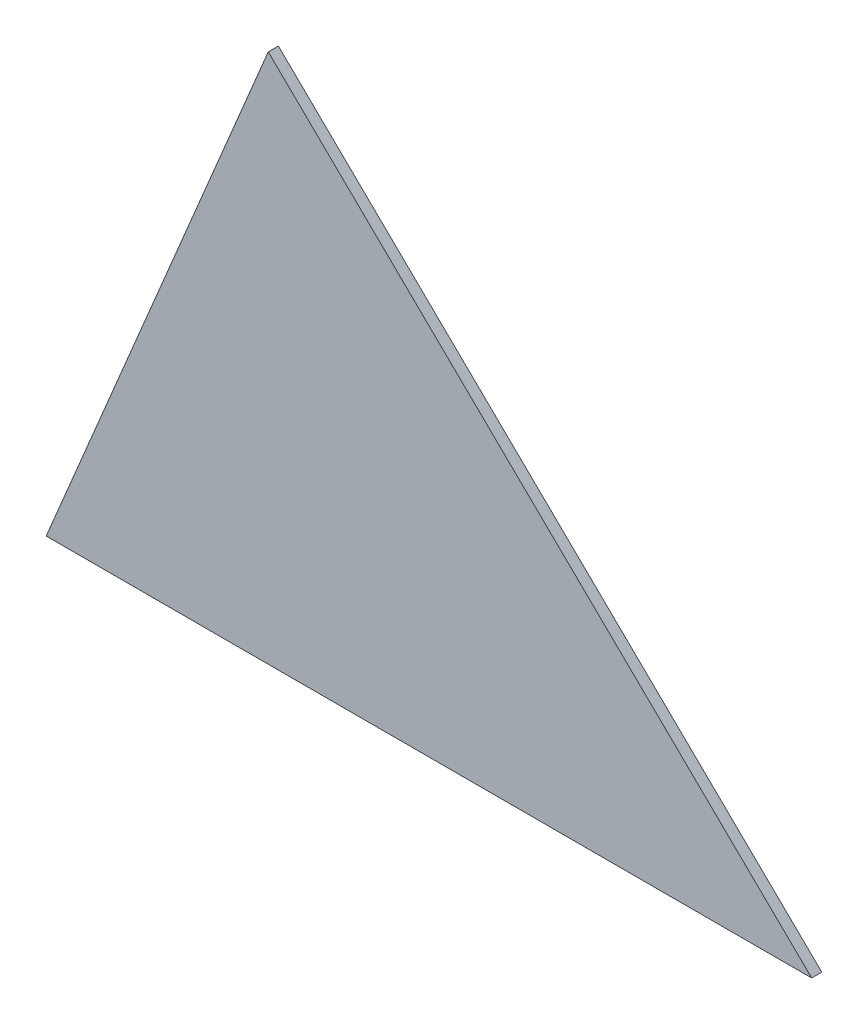
SolidWorks part; units mm, degrees
ref_plane "Front Plane" through (0, 0, 0) normal (0, 0, 1) x (1, 0, 0)
ref_plane "Top Plane" through (0, 0, 0) normal (0, 1, 0) x (1, 0, 0)
ref_plane "Right Plane" through (0, 0, 0) normal (1, 0, 0) x (0, 0, -1)
sketch "Sketch1" plane through (0, 0, 0) normal (0, 0, 1) x (1, 0, 0)
  line L0 (-7.9994, 30.3202) -> (-29.9331, -22.0628)
  line L1 (-29.9331, -22.0628) -> (45.6738, -22.0628)
  line L2 (45.6738, -22.0628) -> (-7.9994, 30.3202)
base flange "Base-Flange1" sketch "Sketch1" thickness 1 reverse thickness direction no parameters "D1"=1
sketch "Bend-Lines1" [suppressed] plane through (0, 0, 0) normal (0, 1, 0) x (1, 0, 0)
sketch "Bounding-Box1" [suppressed] plane through (0, 0, 0) normal (0, 1, 0) x (1, 0, 0)
sheet metal parameters "Sheet-Metal1" thickness 1 parameters "D1"=1
flat pattern "Flat-Pattern1" [suppressed]
sketch "Bend-Lines2" plane through (0, 0, 0) normal (0, 1, 0) x (1, 0, 0)
sketch3d "Bounding-Box2" [suppressed]
  line L0 (29.9331, -22.0628, 0) -> (-45.6738, -22.0628, 0) construction
  line L1 (29.9331, 30.3202, 0) -> (-45.6738, 30.3202, 0) construction
  line L2 (29.9331, -22.0628, 0) -> (29.9331, 30.3202, 0) construction
  line L3 (-45.6738, -22.0628, 0) -> (-45.6738, 30.3202, 0) construction
